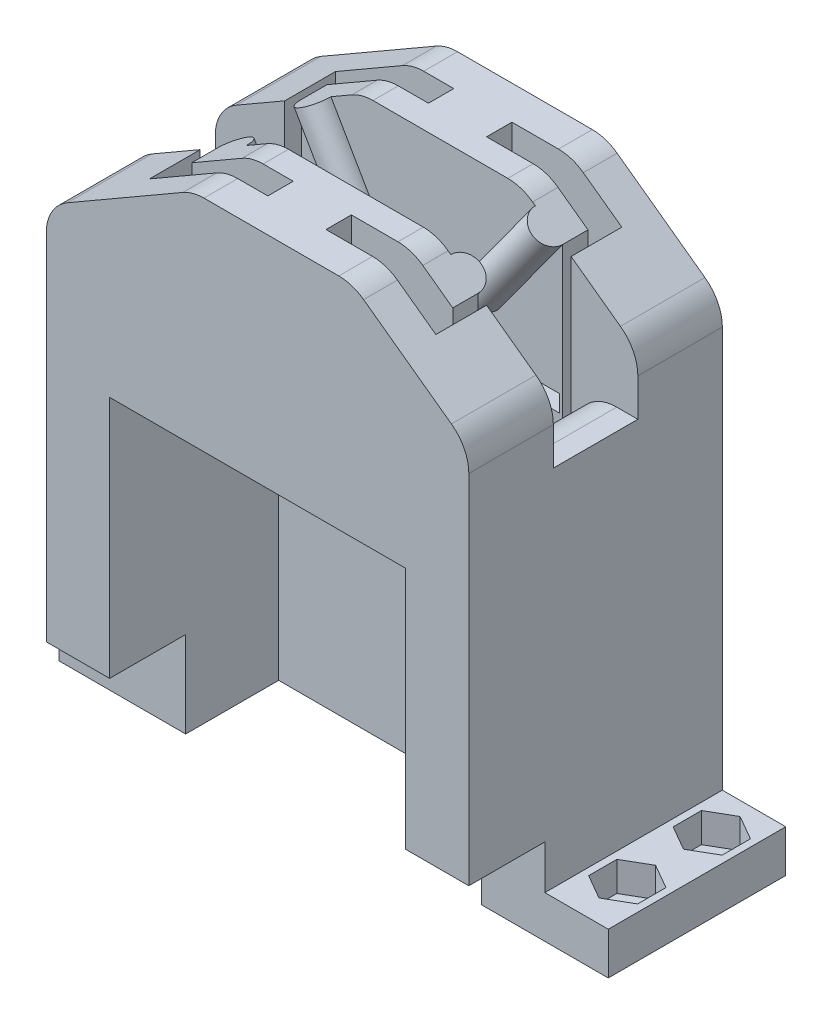
SolidWorks part; units mm, degrees
ref_plane "Front Plane" through (0, 0, 0) normal (0, 0, 1) x (1, 0, 0)
ref_plane "Top Plane" through (0, 0, 0) normal (0, 1, 0) x (1, 0, 0)
ref_plane "Right Plane" through (0, 0, 0) normal (1, 0, 0) x (0, 0, -1)
sketch "Sketch1" plane through (0, 0, 0) normal (0, 0, 1) x (1, 0, 0)
  line L0 (0.5834, 17.8723) -> (-16.7371, 7.8723)
  line L1 (-16.7371, 17.8723) -> (33.2629, 17.8723)
  line L2 (-16.7371, 17.8723) -> (-16.7371, -47.1277)
  line L3 (-16.7371, -47.1277) -> (33.2629, -47.1277)
  line L4 (33.2629, 17.8723) -> (33.2629, -47.1277)
  line L5 (19.4991, 17.8723) -> (33.2629, 7.8723)
  dimension "D1" = 50
  dimension "D2" = 65
  dimension "D3" = 0
  dimension "D4" = 0
  dimension "D5" = 60
  dimension "D6" = 0
  dimension "D7" = 0
  dimension "D8" = 54
  dimension "D9" = 10
  dimension "D10" = 10
extrude "Boss-Extrude1" add sketch "Sketch1" along normal blind 30 contours L5 L1 L0 L2 L3 L4 region at (8.347, -16.0926, 0)
sketch "Sketch2" plane through (0, 17.8723, 0) normal (0, 1, 0) x (1, 0, 0)
  line L0 (0.5834, 0) -> (19.4991, 0) construction
  line L1 (-16.7371, -10) -> (33.2629, -10)
  line L2 (-16.7371, -10) -> (-16.7371, -20)
  line L3 (-16.7371, -20) -> (33.2629, -20)
  line L4 (33.2629, -10) -> (33.2629, -20)
  line L5 (0.5834, -30) -> (19.4991, -30) construction
  line L6 (33.2629, -30) -> (33.2629, 0) construction
  line L7 (-16.7371, -30) -> (-16.7371, 0) construction
  dimension "D1" = 10
  dimension "D2" = 10
  dimension "D3" = 0
  dimension "D4" = 0
extrude "Cut-Extrude1" cut sketch "Sketch2" against normal blind 25
sketch "Sketch3" plane through (0, -47.1277, 0) normal (0, -1, 0) x (1, 0, 0)
  line L0 (-16.7371, 30) -> (33.2629, 30) construction
  line L1 (-9.2371, 20) -> (25.7629, 20)
  line L2 (-9.2371, 20) -> (-9.2371, 10)
  line L3 (-9.2371, 10) -> (25.7629, 10)
  line L4 (25.7629, 20) -> (25.7629, 10)
  line L5 (-16.7371, 0) -> (33.2629, 0) construction
  line L6 (33.2629, 30) -> (33.2629, 0) construction
  line L7 (-16.7371, 30) -> (-16.7371, 0) construction
  dimension "D1" = 10
  dimension "D2" = 10
  dimension "D3" = 7.5
  dimension "D4" = 7.5
sketch "Sketch4" plane through (-7.5931, 13.1516, 0) normal (-0.5, 0.866, 0) x (0, 0, 1)
  line L0 (10, -10.5586) -> (10, 9.4414) construction
  line L1 (10, -10.5586) -> (0, -10.5586) construction
  line L2 (20, 9.4414) -> (20, -10.5586) construction
  line L3 (30, -10.5586) -> (20, -10.5586) construction
  circle A0 centre (10, 3.2414) radius 2
  circle A1 centre (20, 3.2414) radius 2
  dimension "D2" = 13.8
  dimension "D4" = 4
  dimension "D5" = 4
  dimension "D6" = 13.8
  dimension "D1" = 0
  dimension "D3" = 0
extrude "Boss-Extrude2" add sketch "Sketch4" against normal blind 15
sketch "Sketch6" plane through (0, 17.8723, 0) normal (0, 1, 0) x (1, 0, 0)
  line L0 (19.4991, -10) -> (0.5834, -10) construction
  line L1 (-6.518, -4) -> (5.482, -4)
  line L2 (-6.518, -4) -> (-6.518, -7)
  line L3 (-6.518, -7) -> (5.482, -7)
  line L4 (5.482, -4) -> (5.482, -7)
  line L5 (-16.7371, -10) -> (-6.518, -10) construction
  line L6 (-6.518, -4) -> (-8.518, -4)
  line L7 (-6.518, -4) -> (-6.518, -10)
  line L8 (-6.518, -10) -> (-8.518, -10)
  line L9 (-8.518, -4) -> (-8.518, -10)
  line L10 (-6.518, -20) -> (-16.7371, -20) construction
  line L11 (-6.518, -23) -> (5.482, -23)
  line L12 (-6.518, -23) -> (-6.518, -26)
  line L13 (-6.518, -26) -> (5.482, -26)
  line L14 (5.482, -23) -> (5.482, -26)
  line L15 (-8.518, -20) -> (-6.518, -20)
  line L16 (-8.518, -20) -> (-8.518, -26)
  line L17 (-8.518, -26) -> (-6.518, -26)
  line L18 (-6.518, -20) -> (-6.518, -26)
  line L19 (0.5834, -20) -> (19.4991, -20) construction
  line M8 (0.5834, 0) -> (0.5834, -10)
  dimension "D1" = 0
  dimension "D2" = 3
  dimension "D3" = 12
  dimension "D4" = 3
  dimension "D5" = 0
  dimension "D6" = 0
  dimension "D7" = 2
  dimension "D8" = 0
  dimension "D9" = 0
  dimension "D10" = 0
  dimension "D11" = 2
  dimension "D12" = 0
  dimension "D13" = 0
  dimension "D14" = 3
  dimension "D15" = 3
  dimension "D16" = 12
extrude "Cut-Extrude15" cut sketch "Sketch6" against normal blind 24 contours L4 L1 L3 M8 | L2 L3 L1 M8 | L14 L11 L12 L13 | L18 L15 L16 L17 L12 | L9 L8 L7 L6 region at (-2.9673, 17.8723, 5.5) region at (3.0327, 17.8723, 5.5) region at (-0.518, 17.8723, 24.5) region at (-7.518, 17.8723, 23)
sketch "Sketch7" plane through (0, 0, 10) normal (0, 0, 1) x (1, 0, 0)
  line L0 (-6.518, -6.1277) -> (-8.518, -6.1277) construction
  line L1 (-6.518, -1.1277) -> (23.982, -1.1277)
  line L2 (-6.518, -1.1277) -> (-6.518, -3.1277)
  line L3 (-6.518, -3.1277) -> (23.982, -3.1277)
  line L4 (23.982, -1.1277) -> (23.982, -3.1277)
  line L6 (-6.518, -6.1277) -> (-6.518, 13.7723) construction
  dimension "D1" = 0
  dimension "D2" = 3
  dimension "D3" = 2
  dimension "D4" = 30.5
extrude "Cut-Extrude16" cut sketch "Sketch7" against normal blind 3 and the other way blind 13
sketch "Sketch8" plane through (0, 0, 30) normal (0, 0, 1) x (1, 0, 0)
  line L0 (-16.7371, -47.1277) -> (33.2629, -47.1277) construction
  line L1 (-9.2371, -8.1277) -> (25.7629, -8.1277)
  line L2 (-9.2371, -8.1277) -> (-9.2371, -47.1277)
  line L3 (-9.2371, -47.1277) -> (25.7629, -47.1277)
  line L4 (25.7629, -8.1277) -> (25.7629, -47.1277)
  line L5 (33.2629, 7.8723) -> (33.2629, -47.1277) construction
  line L6 (-16.7371, 7.8723) -> (-16.7371, -47.1277) construction
  point P6 (33.2629, -19.6277)
  dimension "D1" = 0
  dimension "D2" = 39
  dimension "D3" = 7.5
  dimension "D4" = 7.5
extrude "Cut-Extrude17" cut sketch "Sketch8" against normal up to surface (10 mm away) up to face at (3.5509, 3.6584, 20)
sketch "Sketch9" plane through (0, 0, 10) normal (0, 0, 1) x (1, 0, 0)
  line L1 (25.7629, -47.1277) -> (-9.2371, -47.1277) construction
  circle A0 centre (6.8891, -17.1277) radius 11.05
  dimension "D1" = 22.1
  dimension "D2" = 30
extrude "Cut-Extrude18" cut sketch "Sketch3" against normal up to surface (40 mm away) up to face at (8.2629, -7.1277, 15)
extrude "Cut-Extrude19" cut sketch "Sketch9" against normal blind 8
fillet "Fillet5" radius 5 1 edges at (-16.7371, 7.8723, 5) type face fillet first side face at (-8.2239, 12.7874, 4.6667) second side face at (-16.7371, -9.6277, 15)
fillet "Fillet6" radius 5 1 edges at (-16.7371, 7.8723, 25) type face fillet first side face at (-8.2239, 12.7874, 25.3333) second side face at (-16.7371, -10.3494, 15)
fillet "Fillet7" radius 5 1 edges at (0.5834, 17.8723, 2) type face fillet first side face at (-7.3906, 13.2685, 4.6667) second side face at (6.2308, 17.8723, 5.25)
fillet "Fillet8" radius 5 1 edges at (0.5834, 17.8723, 8.5) type face fillet first side face at (-2.9846, 15.8123, 9.2) second side face at (6.5658, 17.8723, 5.25)
fillet "Fillet9" radius 5 1 edges at (0.5834, 17.8723, 21.5) type face fillet first side face at (-2.9846, 15.8123, 20.8) second side face at (6.537, 17.8723, 24.75)
fillet "Fillet10" radius 5 1 edges at (0.5834, 17.8723, 28) type face fillet first side face at (-7.3906, 13.2685, 25.3333) second side face at (6.8719, 17.8723, 24.75)
sketch "Sketch10" plane through (33.2629, 0, 0) normal (1, 0, 0) x (0, 0, -1)
  line L0 (-30, -47.1277) -> (0, -47.1277) construction
  line L1 (-30, -36.9277) -> (-21, -36.9277)
  line L2 (-30, -36.9277) -> (-30, -47.1277)
  line L3 (-30, -47.1277) -> (-21, -47.1277)
  line L4 (-21, -36.9277) -> (-21, -47.1277)
  line L5 (-30, 7.8723) -> (-30, -47.1277) construction
  dimension "D1" = 0
  dimension "D2" = 0
  dimension "D3" = 9
  dimension "D4" = 10.2
extrude "Cut-Extrude20" cut sketch "Sketch10" against normal through all
sketch "Sketch11" plane through (15.2355, 20.9699, 0) normal (0.5878, 0.809, 0) x (0, 0, -1)
  line L0 (-20, -5.27) -> (-20, -22.2831) construction
  line L1 (-10, -22.2831) -> (-10, -5.27) construction
  line L2 (-10, -22.2831) -> (0, -22.2831) construction
  line L3 (-30, -22.2831) -> (-20, -22.2831) construction
  circle A0 centre (-20, -9.2831) radius 2
  circle A1 centre (-10, -9.2831) radius 2
  dimension "D2" = 4
  dimension "D4" = 4
  dimension "D6" = 13
  dimension "D1" = 0
  dimension "D3" = 0
  dimension "D5" = 13
extrude "Boss-Extrude3" add sketch "Sketch11" against normal blind 13
sketch "Sketch13" plane through (0, 17.8723, 0) normal (0, 1, 0) x (1, 0, 0)
  line L1 (12.3637, -26) -> (24.3637, -26)
  line L2 (12.3637, -26) -> (12.3637, -23)
  line L3 (12.3637, -23) -> (24.3637, -23)
  line L4 (24.3637, -26) -> (24.3637, -23)
  line L5 (24.3637, -26) -> (25.3637, -26)
  line L6 (24.3637, -26) -> (24.3637, -16.4293)
  line L7 (24.3637, -16.4293) -> (25.3637, -16.4293)
  line L8 (25.3637, -26) -> (25.3637, -16.4293)
  line L9 (12.3637, -7) -> (24.3637, -7)
  line L10 (12.3637, -7) -> (12.3637, -4)
  line L11 (12.3637, -4) -> (24.3637, -4)
  line L12 (24.3637, -7) -> (24.3637, -4)
  line L13 (24.3637, -11.2788) -> (25.3637, -11.2788)
  line L14 (24.3637, -11.2788) -> (24.3637, -4)
  line L15 (24.3637, -4) -> (25.3637, -4)
  line L16 (25.3637, -11.2788) -> (25.3637, -4)
  line L17 (1.9232, -20) -> (19.4991, -20) construction
  line L18 (19.4991, -10) -> (1.9232, -10) construction
  line M4 (19.4991, -30) -> (19.4991, -20)
  dimension "D1" = 3
  dimension "D2" = 3
  dimension "D3" = 0
  dimension "D4" = 0
  dimension "D5" = 0
  dimension "D6" = 1
  dimension "D7" = 1
  dimension "D8" = 0
  dimension "D9" = 3
  dimension "D10" = 3
  dimension "D11" = 0
  dimension "D12" = 0
  dimension "D13" = 12
  dimension "D14" = 12
extrude "Cut-Extrude22" cut sketch "Sketch13" against normal blind 23 contours L3 L2 L1 M4 | L1 L4 L3 M4 | L5 L8 L7 L6 L4 | L13 L16 L15 L12 L14 | L9 L12 L11 L10 region at (15.9314, 17.8723, 24.5) region at (21.9314, 17.8723, 24.5) region at (24.8637, 17.8723, 21.2147) region at (18.3637, 17.8723, 5.5) region at (24.8637, 17.8723, 7.6394)
sketch "Sketch14" plane through (-16.7371, 0, 0) normal (-1, 0, 0) x (0, 0, 1)
  line L0 (21, -47.1277) -> (21, -36.9277) construction
  line L1 (0, -42.1277) -> (21, -42.1277)
  line L2 (0, -42.1277) -> (0, -47.1277)
  line L3 (0, -47.1277) -> (21, -47.1277)
  line L4 (21, -42.1277) -> (21, -47.1277)
  line L5 (21, -47.1277) -> (0, -47.1277) construction
  line L6 (0, 4.9855) -> (0, -47.1277) construction
  dimension "D1" = 5
  dimension "D2" = 0
  dimension "D3" = 0
  dimension "D4" = 0
extrude "Boss-Extrude4" add sketch "Sketch14" along normal blind 7.5
sketch "Sketch15" plane through (33.2629, 0, 0) normal (1, 0, 0) x (0, 0, -1)
  line L0 (-21, -47.1277) -> (-21, -36.9277) construction
  line L1 (-21, -42.1277) -> (0, -42.1277)
  line L2 (-21, -42.1277) -> (-21, -47.1277)
  line L3 (-21, -47.1277) -> (0, -47.1277)
  line L4 (0, -42.1277) -> (0, -47.1277)
  line L5 (-21, -47.1277) -> (0, -47.1277) construction
  line L6 (0, 7.8723) -> (0, -47.1277) construction
  dimension "D1" = 0
  dimension "D2" = 0
  dimension "D3" = 0
  dimension "D4" = 5
extrude "Boss-Extrude5" add sketch "Sketch15" along normal blind 7.5
sketch "Sketch16" plane through (0, -42.1277, 0) normal (0, 1, 0) x (1, 0, 0)
  line L0 (40.7629, 0) -> (40.7629, -21) construction
  line L1 (37.0129, -11.6514) -> (34.1129, -13.3257)
  line L2 (34.1129, -13.3257) -> (34.1129, -16.6743)
  line L3 (34.1129, -16.6743) -> (37.0129, -18.3486)
  line L4 (37.0129, -18.3486) -> (39.9129, -16.6743)
  line L5 (39.9129, -16.6743) -> (39.9129, -13.3257)
  line L6 (39.9129, -13.3257) -> (37.0129, -11.6514)
  line L7 (37.0129, -1.6514) -> (34.1129, -3.3257)
  line L8 (34.1129, -3.3257) -> (34.1129, -6.6743)
  line L9 (34.1129, -6.6743) -> (37.0129, -8.3486)
  line L10 (37.0129, -8.3486) -> (39.9129, -6.6743)
  line L11 (39.9129, -6.6743) -> (39.9129, -3.3257)
  line L12 (39.9129, -3.3257) -> (37.0129, -1.6514)
  line L13 (40.7629, 0) -> (33.2629, 0) construction
  circle A0 centre (37.0129, -15) radius 2.9 construction
  circle A1 centre (37.0129, -5) radius 2.9 construction
  dimension "D3" = 5.8
  dimension "D4" = 5.8
  dimension "D7" = 5
  dimension "D8" = 10
  dimension "D1" = 0
  dimension "D2" = 0
  dimension "D5" = 3.75
  dimension "D6" = 3.75
extrude "Cut-Extrude23" cut sketch "Sketch16" against normal blind 3.5
sketch "Sketch17" plane through (0, -45.6277, 0) normal (0, 1, 0) x (1, 0, 0)
  line L1 (40.7629, 0) -> (40.7629, -21) construction
  line L2 (40.7629, 0) -> (33.2629, 0) construction
  circle A0 centre (37.0129, -15) radius 1.425
  circle A1 centre (37.0129, -5) radius 1.425
  dimension "D1" = 2.85
  dimension "D2" = 2.85
  dimension "D3" = 3.75
  dimension "D4" = 3.75
  dimension "D5" = 5
  dimension "D6" = 10
extrude "Cut-Extrude24" cut sketch "Sketch17" against normal through all
sketch "Sketch19" plane through (0, -7.1277, 0) normal (0, 1, 0) x (1, 0, 0)
  line L0 (-9.2371, -20) -> (-9.2371, -10) construction
  line L1 (-9.2371, -10) -> (-16.7371, -10)
  line L2 (-9.2371, -10) -> (-9.2371, -20)
  line L3 (-9.2371, -20) -> (-16.7371, -20)
  line L4 (-16.7371, -10) -> (-16.7371, -20)
  line L5 (33.2629, -10) -> (25.7629, -10)
  line L6 (33.2629, -10) -> (33.2629, -20)
  line L7 (33.2629, -20) -> (25.7629, -20)
  line L8 (25.7629, -10) -> (25.7629, -20)
  line L9 (-9.2371, -10) -> (-16.7371, -10) construction
  line L10 (-16.7371, -10) -> (-16.7371, -20) construction
  line L11 (-16.7371, -20) -> (-9.2371, -20) construction
  line L12 (33.2629, -10) -> (25.7629, -10) construction
  line L13 (33.2629, -20) -> (33.2629, -10) construction
  line L14 (25.7629, -10) -> (25.7629, -20) construction
  line L15 (25.7629, -20) -> (33.2629, -20) construction
  dimension "D1" = 0
  dimension "D2" = 0
  dimension "D3" = 0
  dimension "D4" = 0
  dimension "D5" = 0
  dimension "D6" = 0
  dimension "D7" = 0
  dimension "D8" = 0
extrude "Boss-Extrude7" add sketch "Sketch19" along normal blind 8
fillet "Fillet14" radius 5 1 edges at (-9.2371, 0.8723, 15) type face fillet first side face at (-12.9871, 0.8723, 15) second side face at (-9.2371, -22.8277, 20.25)
fillet "Fillet18" radius 5 1 edges at (25.7629, 0.8723, 15) type face fillet first side face at (29.5129, 0.8723, 15) second side face at (25.7629, -22.8277, 20.25)
fillet "Fillet19" radius 5 1 edges at (33.2629, 7.8723, 5) type face fillet first side face at (26.0419, 13.1186, 4.6667) second side face at (33.2629, -10.2477, 15.15)
fillet "Fillet20" radius 5 1 edges at (33.2629, 7.8723, 25) type face fillet first side face at (26.0419, 13.1186, 25.3333) second side face at (33.2629, -10.8846, 15.15)
fillet "Fillet21" radius 5 1 edges at (19.4991, 17.8723, 2) type face fillet first side face at (9.9668, 17.8723, 5.3333) second side face at (25.3549, 13.6178, 4.6667)
fillet "Fillet22" radius 5 1 edges at (19.4991, 17.8723, 8.5) type face fillet first side face at (9.696, 17.8723, 5.3333) second side face at (21.7707, 16.2219, 9.2)
fillet "Fillet23" radius 5 1 edges at (19.4991, 17.8723, 28) type face fillet first side face at (10.115, 17.8723, 24.6667) second side face at (25.3549, 13.6178, 25.3333)
fillet "Fillet24" radius 5 1 edges at (19.4991, 17.8723, 21.5) type face fillet first side face at (9.8443, 17.8723, 24.6667) second side face at (21.7707, 16.2219, 20.8)
